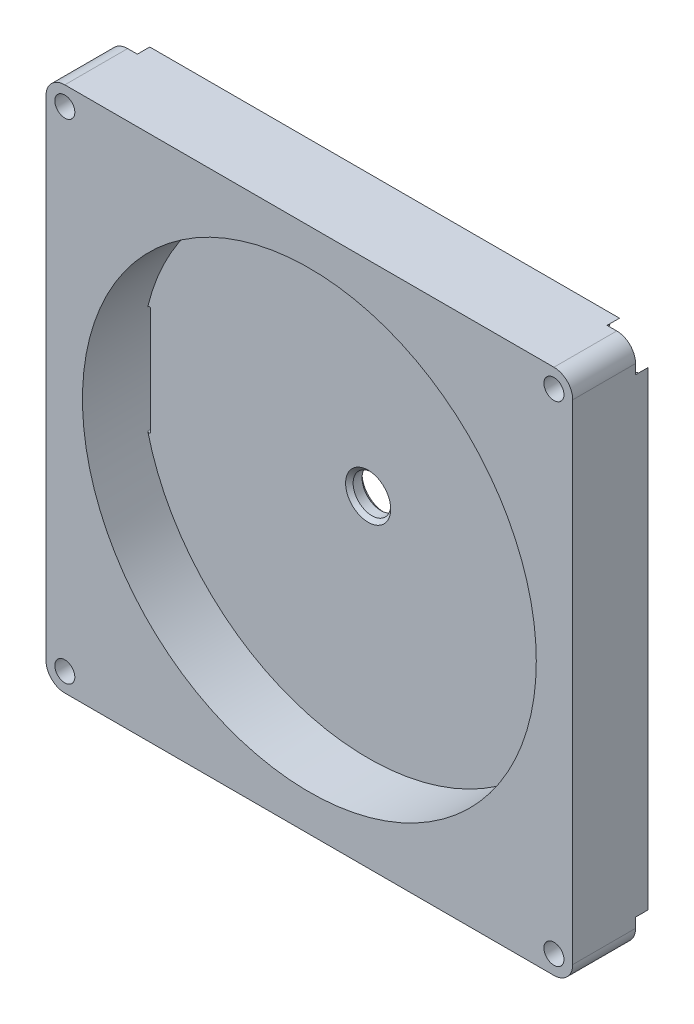
SolidWorks part; units mm, degrees
material "6061 Alloy"
ref_plane "Front Plane" through (0, 0, 0) normal (0, 0, 1) x (1, 0, 0)
ref_plane "Top Plane" through (0, 0, 0) normal (0, 1, 0) x (1, 0, 0)
ref_plane "Right Plane" through (0, 0, 0) normal (1, 0, 0) x (0, 0, -1)
sketch "Sketch1" plane through (0, 0, 0) normal (0, 0, 1) x (1, 0, 0)
  line L0 (-88.9, 88.9) -> (-88.9, -88.9)
  line L1 (-88.9, -88.9) -> (88.9, -88.9)
  line L2 (88.9, -88.9) -> (88.9, 88.9)
  line L3 (88.9, 88.9) -> (-88.9, 88.9)
  line L4 (-88.9, 88.9) -> (88.9, -88.9) construction
  line L5 (88.9, 88.9) -> (-88.9, -88.9) construction
  point P2 (0, 0)
  dimension "D1" = 177.8
extrude "Boss-Extrude1" add sketch "Sketch1" along normal mid plane 25.4
sketch "Sketch2" plane through (0, 0, 12.7) normal (0, 0, 1) x (1, 0, 0)
  line L0 (0, 0) -> (-88.9, 0) construction
  line L1 (-88.9, 88.9) -> (-88.9, -88.9) construction
  circle A0 centre (0, 0) radius 76.5969
  dimension "D1" = 153.1937
extrude "Cut-Extrude1" cut sketch "Sketch2" against normal blind 19.8438
sketch "Sketch3" plane through (0, 0, -7.1438) normal (0, 0, 1) x (1, 0, 0)
  circle A0 centre (0, 0) radius 6.35
  dimension "D1" = 12.7
extrude "Cut-Extrude2" cut sketch "Sketch3" against normal blind 19.8438
sketch "Sketch5" plane through (0, 0, -7.1438) normal (0, 0, 1) x (1, 0, 0)
  line L0 (0, 0) -> (-76.5969, 0) construction
  line L1 (-73.4219, 21.8245) -> (-73.4219, -21.8245)
  line L6 (-6.35, 76.708) -> (6.35, 76.708)
  line L7 (63.8969, 30.0687) -> (63.8969, -30.0687)
  line L8 (-6.35, 76.708) -> (-6.35, 70.358)
  line L9 (-6.35, 70.358) -> (6.35, 70.358)
  line L10 (6.35, 70.358) -> (6.35, 76.708)
  line L11 (0, 0) -> (0, 76.5969) construction
  line L12 (0, 0) -> (76.5969, 0) construction
  line L13 (63.8969, -30.0687) -> (70.4482, -30.0687)
  line L14 (63.8969, 30.0687) -> (70.4482, 30.0687)
  circle A0 centre (0, 0) radius 76.5969 construction
  arc A1 (-73.4219, 21.8245) -> (-73.4219, -21.8245) centre (0, 0) ccw
  circle A2 centre (0, 0) radius 76.5969 construction
  circle A3 centre (0, 0) radius 6.35 construction
  arc A5 (70.4482, -30.0687) -> (70.4482, 30.0687) centre (0, 0) ccw
  point P9 (0, 76.708)
  dimension "D1" = 3.175
  dimension "D2" = 70.358
  dimension "D3" = 12.7
  dimension "D4" = 6.35
  dimension "D5" = 12.7
  dimension "D6" = 70.4482
extrude "Cut-Extrude3" cut sketch "Sketch5" against normal blind 19.8438
fillet "Fillet1" radius 6.35 4 edges at (-88.9, -88.9, 0) (88.9, -88.9, 0) (-88.9, 88.9, 0) (88.9, 88.9, 0)
fillet "Fillet2" radius 0.635 4 edges at (-6.35, 76.708, -9.9219) (6.35, 76.708, -9.9219) (6.35, 70.358, -9.9219) (-6.35, 70.358, -9.9219)
fillet "Fillet3" radius 0.508 2 edges at (-73.4219, -21.8245, -9.9219) (-73.4219, 21.8245, -9.9219)
chamfer "Chamfer2" distance 1.27 angle 45 2 edges at (6.35, 0, -7.1438) (6.35, 0, -12.7)
fillet "Fillet5" radius 0.762 4 edges at (63.8969, 30.0687, -9.9219) (63.8969, -30.0687, -9.9219) (70.4482, 30.0687, -9.9219) (70.4482, -30.0687, -9.9219)
ref_point "Point1"
ref_point "Point2"
ref_point "Point3"
ref_point "Point4"
hole_wizard "CBORE for 1/4 Binding Head Machine Screw1" positions "Sketch6" profile "Sketch7" counterbore size "1/4" standard "ANSI Inch" end condition through all
sketch "Sketch6" plane through (0, 0, -12.7) normal (0, 0, -1) x (-1, 0, 0)
  point P0 (-82.55, 82.55)
  point P3 (82.55, 82.55)
  point P6 (82.55, -82.55)
  point P9 (-82.55, -82.55)
sketch "Sketch7" plane through (82.55, 82.55, -12.7) normal (1, 0, 0) x (0, 1, 0)
  line L0 (0, 0) -> (0, 25.4)
  line L1 (0, 25.4) -> (3.3782, 25.4)
  line L3 (3.3782, 25.4) -> (3.3782, 4.191)
  line L4 (3.3782, 4.191) -> (7.1437, 4.191)
  line L5 (7.1437, 4.191) -> (7.1437, 0)
  line L7 (7.1437, 0) -> (0, 0)
  line L11 (0, -6.35) -> (0, 107.95) construction
  dimension "Thru Hole Dia." = 6.7564
  dimension "Thru Hole Depth" = 25.4
  dimension "C'Bore Dia." = 14.2875
  dimension "C'Bore Depth" = 4.191
